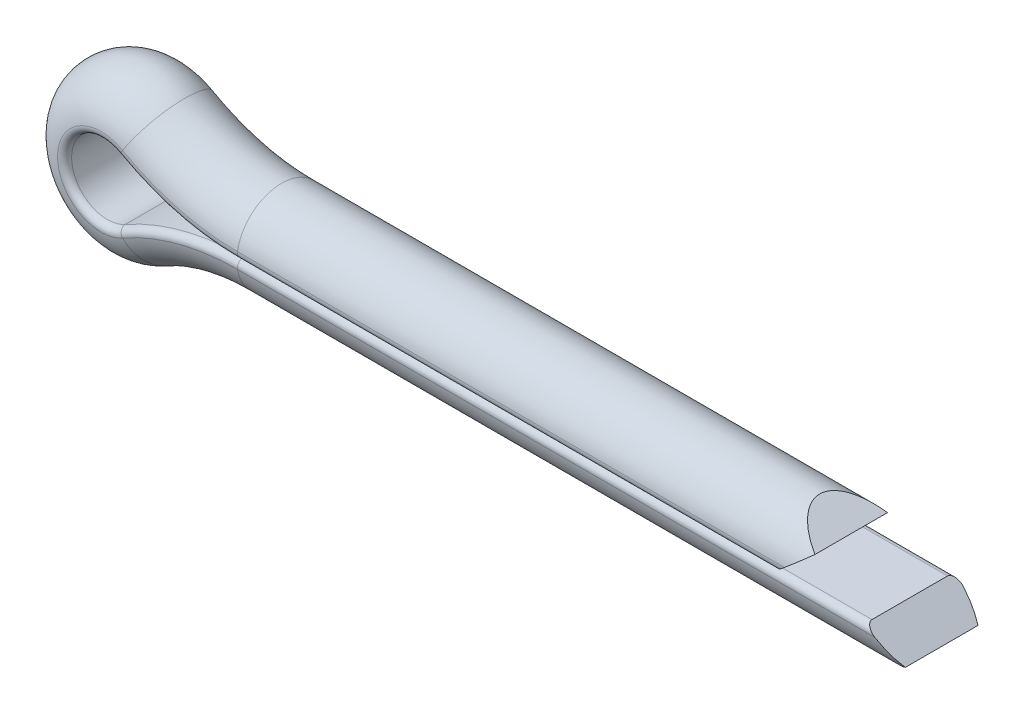
SolidWorks part; units mm, degrees
ref_plane "Front Plane" through (0, 0, 0) normal (0, 0, 1) x (1, 0, 0)
ref_plane "Top Plane" through (0, 0, 0) normal (0, 1, 0) x (1, 0, 0)
ref_plane "Right Plane" through (0, 0, 0) normal (1, 0, 0) x (0, 0, -1)
sketch "PathSke" plane through (0, 0, 0) normal (0, 0, 1) x (1, 0, 0)
  line L0 (0, 0) -> (38.8652, 0) construction
  line L1 (0, 0) -> (0, 12.2501) construction
  line L2 (4.7854, 0) -> (4.7854, 12.2501) construction
  line L3 (4.7854, 1.5748) -> (24.7854, 1.5748)
  line L4 (4.7854, -1.5748) -> (27.9604, -1.5748)
  line L5 (0, 0) -> (-2.8346, 0) construction
  arc A0 (1.3958, 2.4672) -> (1.3958, -2.4672) centre (0, 0) ccw
  arc A1 (4.7854, 1.5748) -> (1.3958, 2.4672) centre (4.7854, 8.4584) cw
  arc A2 (4.7854, -1.5748) -> (1.3958, -2.4672) centre (4.7854, -8.4584) ccw
  dimension "Diameter" = 3.1496
  dimension "Head_height" = 7.62
ref_plane "SectionPlane" through (24.7854, 1.5748, 0) normal (1, 0, 0) x (0, 0, -1)
sketch "SectionSke" plane through (24.7854, 1.5748, 0) normal (1, 0, 0) x (0, 0, -1)
  line L0 (0, -1.5748) -> (0, 8.6928) construction
  line L1 (0, -1.5748) -> (0, 10.6753) construction
  line L2 (-1.45, -1.5748) -> (1.45, -1.5748) construction
  line L3 (-1.3263, -1.5728) -> (1.3263, -1.5728)
  arc A0 (1.5515, -1.305) -> (-1.5515, -1.305) centre (0, -1.5748) ccw
  arc A1 (-1.3263, -1.5728) -> (-1.5515, -1.305) centre (-1.3263, -1.3442) cw
  arc A2 (1.5515, -1.305) -> (1.3263, -1.5728) centre (1.3263, -1.3442) cw
  dimension "D1" = 0.002
  dimension "Diameter" = 3.1496
sweep "BaseBody" add profiles "SectionSke" path "PathSke"
sketch "ConeCutSke" plane through (0, 0, 0) normal (0, 0, 1) x (1, 0, 0)
  line L0 (0, 0) -> (34.6884, 0) construction
  line L1 (23.6638, 1.5848) -> (27.9704, 1.5848)
  line L2 (27.9704, 1.5848) -> (27.9704, -1.5848)
  line L3 (24.7854, 1.5748) -> (4.7854, 1.5748) construction
  line L4 (23.6638, 1.5848) -> (24.7854, 0.9223)
  line L5 (24.7854, 0.2698) -> (24.7854, 1.5748) construction
  line L6 (24.7854, 0.9223) -> (23.6638, 0)
  line L7 (23.6638, 0) -> (26.8388, 0)
  line L8 (26.8388, 0) -> (27.9604, -0.9223)
  line L9 (27.9604, -1.5748) -> (27.9604, -0.2698) construction
  line L10 (27.9604, -0.9223) -> (26.8388, -1.5848)
  line L11 (26.8388, -1.5848) -> (27.9704, -1.5848)
  point P19 (27.9704, 0)
  dimension "D1" = 0.01
  dimension "D2" = 70
  dimension "D3" = 70
  dimension "D4" = 0.01
extrude "ConeCut" cut sketch "ConeCutSke" against normal through all and the other way through all
equation "\"Diameter@SectionSke\" = \"Diameter@PathSke\""
equation "\"Head_dia@PathSke\" = \"Diameter@PathSke\"*1.8"
